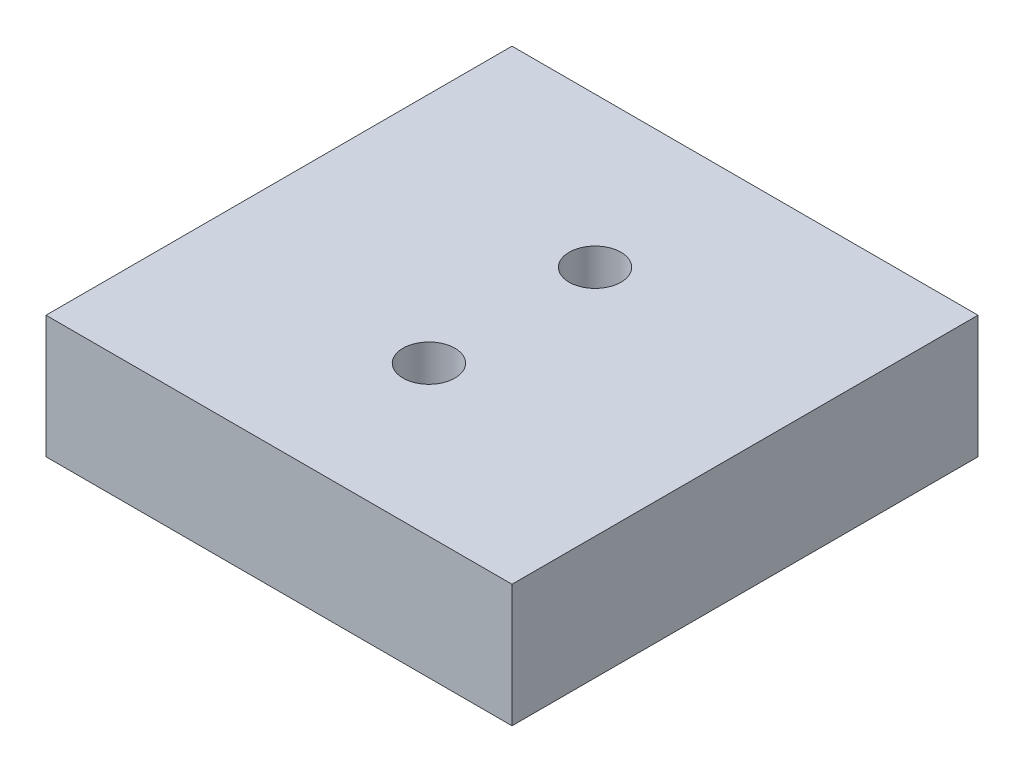
SolidWorks part; units mm, degrees
ref_plane "Front Plane" through (0, 0, 0) normal (0, 0, 1) x (1, 0, 0)
ref_plane "Top Plane" through (0, 0, 0) normal (0, 1, 0) x (1, 0, 0)
ref_plane "Right Plane" through (0, 0, 0) normal (1, 0, 0) x (0, 0, -1)
sketch "Sketch1" plane through (0, 0, 0) normal (0, 1, 0) x (1, 0, 0)
  line L1 (-28.5, 28.5) -> (28.5, 28.5)
  line L2 (-28.5, 28.5) -> (-28.5, -28.5)
  line L3 (-28.5, -28.5) -> (28.5, -28.5)
  line L4 (28.5, 28.5) -> (28.5, -28.5)
  line L5 (0, -28.5) -> (0, 28.5) construction
  line L6 (-28.5, 0) -> (28.5, 0) construction
  point P0 (0, 0)
  dimension "D1" = 57
  dimension "D2" = 57
extrude "Boss-Extrude1" add sketch "Sketch1" along normal blind 15
sketch "Sketch2" plane through (0, 15, 0) normal (0, 1, 0) x (1, 0, 0)
  line L0 (0, 28.5) -> (0, -28.5) construction
  line L1 (28.5, 28.5) -> (-28.5, 28.5) construction
  line L2 (-28.5, -28.5) -> (28.5, -28.5) construction
  line L3 (-28.5, 0) -> (28.5, 0) construction
  line L4 (-28.5, 28.5) -> (-28.5, -28.5) construction
  line L5 (28.5, -28.5) -> (28.5, 28.5) construction
  circle A0 centre (0, 10.16) radius 3.175
  circle A1 centre (0, -10.16) radius 3.175
  dimension "D1" = 6.35
  dimension "D2" = 10.16
extrude "Cut-Extrude1" cut sketch "Sketch2" against normal through all
